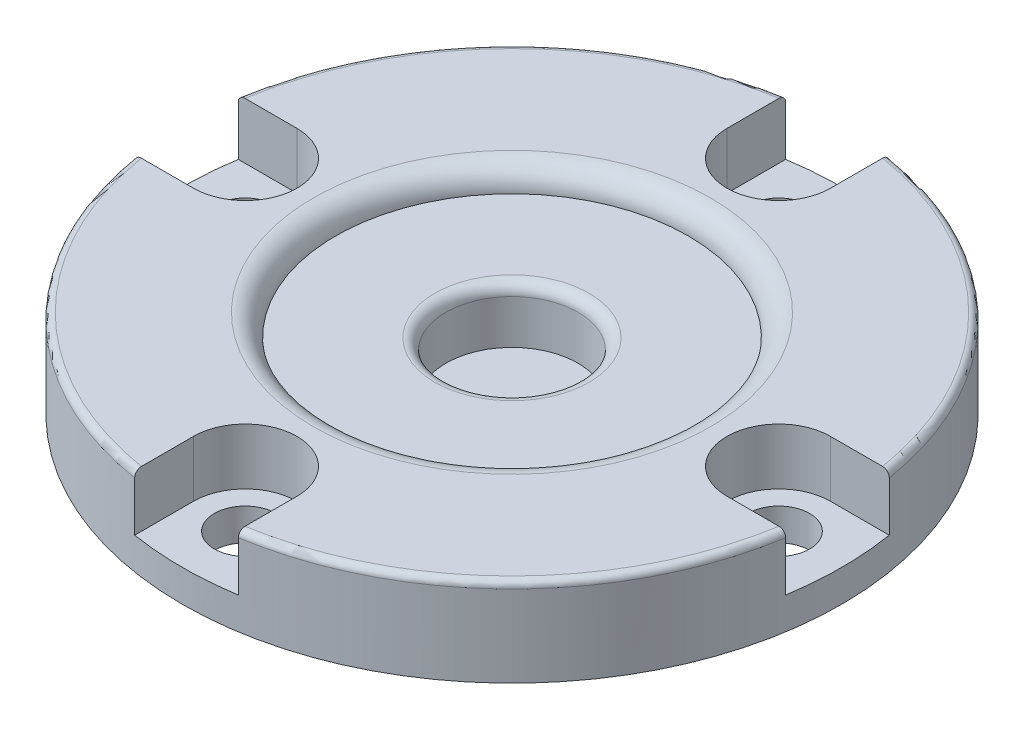
SolidWorks part; units mm, degrees
ref_plane "Front Plane" through (0, 0, 0) normal (0, 0, 1) x (1, 0, 0)
ref_plane "Top Plane" through (0, 0, 0) normal (0, 1, 0) x (1, 0, 0)
ref_plane "Right Plane" through (0, 0, 0) normal (1, 0, 0) x (0, 0, -1)
sketch "Sketch1" plane through (0, 0, 0) normal (0, 1, 0) x (1, 0, 0)
  circle A0 centre (0, 0) radius 14.95
  dimension "D1" = 29.9
extrude "Boss-Extrude1" add sketch "Sketch1" along normal blind 4
sketch "Sketch2" plane through (0, 4, 0) normal (0, 1, 0) x (1, 0, 0)
  line L0 (-2.35, 12.1) -> (-2.35, 14.7641)
  line L1 (2.35, 12.1) -> (2.35, 14.7641)
  line L2 (12.1, -2.35) -> (14.7641, -2.35)
  line L3 (12.1, 2.35) -> (14.7641, 2.35)
  line L4 (-2.35, -12.1) -> (-2.35, -14.7641)
  line L5 (2.35, -12.1) -> (2.35, -14.7641)
  line L6 (-12.1, 2.35) -> (-14.7641, 2.35)
  line L7 (-12.1, -2.35) -> (-14.7641, -2.35)
  circle A0 centre (0, 0) radius 12.1 construction
  arc A1 (-2.35, 12.1) -> (2.35, 12.1) centre (0, 12.1) ccw
  circle A2 centre (0, 0) radius 14.95 construction
  arc A3 (-2.35, 14.7641) -> (2.35, 14.7641) centre (0, 0) cw
  arc A4 (12.1, 2.35) -> (12.1, -2.35) centre (12.1, 0) ccw
  arc A5 (14.7641, 2.35) -> (14.7641, -2.35) centre (0, 0) cw
  arc A6 (2.35, -12.1) -> (-2.35, -12.1) centre (0, -12.1) ccw
  arc A7 (2.35, -14.7641) -> (-2.35, -14.7641) centre (0, 0) cw
  arc A8 (-12.1, -2.35) -> (-12.1, 2.35) centre (-12.1, 0) ccw
  arc A9 (-14.7641, -2.35) -> (-14.7641, 2.35) centre (0, 0) cw
  point P29 (0, 0)
  dimension "D1" = 24.2
  dimension "D2" = 4.7
  dimension "D3" = 4
extrude "Cut-Extrude1" cut sketch "Sketch2" against normal blind 2.55
sketch "Sketch3" plane through (0, 1.45, 0) normal (0, 1, 0) x (1, 0, 0)
  circle A0 centre (0, 12.1) radius 1.4
  circle A1 centre (-12.1, 0) radius 1.4
  circle A2 centre (0, -12.1) radius 1.4
  circle A3 centre (12.1, 0) radius 1.4
  dimension "D1" = 2.8
extrude "Cut-Extrude2" cut sketch "Sketch3" against normal blind 2.55
sketch "Sketch4" plane through (0, 4, 0) normal (0, 1, 0) x (1, 0, 0)
  circle A0 centre (0, 0) radius 8
  dimension "D1" = 16
extrude "Cut-Extrude3" cut sketch "Sketch4" against normal blind 1
sketch "Sketch5" plane through (0, 3, 0) normal (0, 1, 0) x (1, 0, 0)
  circle A0 centre (0, 0) radius 3
  dimension "D1" = 6
extrude "Cut-Extrude4" cut sketch "Sketch5" against normal blind 2.5
fillet "Fillet1" radius 1 1 edges at (0, 4, 8)
fillet "Fillet2" radius 0.5 1 edges at (0, 3, 3)
fillet "Fillet3" radius 0.3 4 edges at (10.5712, 4, 10.5712) (-10.5712, 4, 10.5712) (-10.5712, 4, -10.5712) (10.5712, 4, -10.5712)
